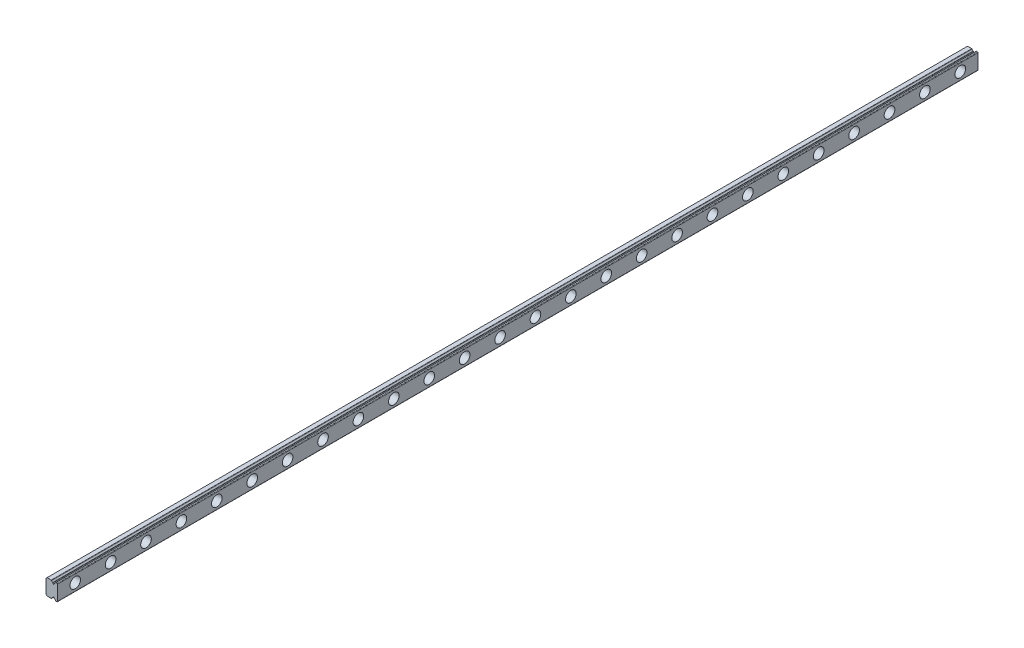
SolidWorks part; units mm, degrees
material "AISI 304"
ref_plane "前视基准面" through (0, 0, 0) normal (0, 0, 1) x (1, 0, 0)
ref_plane "上视基准面" through (0, 0, 0) normal (0, 1, 0) x (1, 0, 0)
ref_plane "右视基准面" through (0, 0, 0) normal (1, 0, 0) x (0, 0, -1)
sketch "草图1" plane through (0, 0, 0) normal (0, 0, 1) x (1, 0, 0)
  line L0 (0, 8.4) -> (0.6, 9)
  line L1 (0.6, 0) -> (2.9423, 0)
  line L2 (0, 0.6) -> (0, 8.4)
  line L3 (0.6, 9) -> (2.9423, 9)
  line L4 (6.5, 0.3) -> (6.5, 8.7)
  line L5 (0, 0.6) -> (0.6, 0)
  line L6 (4.25, 9) -> (4.25, 8) construction
  line L7 (4.25, 9) -> (4.25, 9.3) construction
  line L8 (3.85, 8) -> (3.85, 8.0351)
  line L9 (4.65, 8) -> (4.65, 8.0351)
  line L10 (5.5577, 9) -> (6.2, 9)
  line L11 (6.5, 4.5) -> (0, 4.5) construction
  line L12 (3.85, 8) -> (3.85, 8.0351)
  line L13 (4.65, 8) -> (4.65, 8.0351)
  line L14 (4.25, 0) -> (4.25, -0.3) construction
  line L15 (4.25, 0) -> (4.25, 1) construction
  line L16 (4.65, 1) -> (4.65, 0.9649)
  line L17 (3.85, 1) -> (3.85, 0.9649)
  line L18 (4.65, 1) -> (4.65, 0.9649)
  line L19 (3.85, 1) -> (3.85, 0.9649)
  line L20 (5.5577, 0) -> (6.2, 0)
  arc A0 (3.85, 8) -> (4.65, 8) centre (4.25, 8) ccw
  arc A1 (3.1291, 8.8714) -> (3.7357, 8.2158) centre (4.25, 9.3) ccw
  arc A2 (4.7643, 8.2158) -> (5.3709, 8.8714) centre (4.25, 9.3) ccw
  arc A3 (5.3709, 8.8714) -> (5.5577, 9) centre (5.5577, 8.8) cw
  arc A4 (4.65, 8.0351) -> (4.7643, 8.2158) centre (4.85, 8.0351) cw
  arc A5 (3.85, 8.0351) -> (3.7357, 8.2158) centre (3.65, 8.0351) ccw
  arc A6 (3.1291, 8.8714) -> (2.9423, 9) centre (2.9423, 8.8) ccw
  arc A7 (3.1291, 8.8714) -> (2.9423, 9) centre (2.9423, 8.8) ccw
  arc A8 (5.3709, 8.8714) -> (5.5577, 9) centre (5.5577, 8.8) cw
  arc A9 (4.65, 8.0351) -> (4.7643, 8.2158) centre (4.85, 8.0351) cw
  arc A10 (3.85, 8.0351) -> (3.7357, 8.2158) centre (3.65, 8.0351) ccw
  arc A11 (3.7357, 8.2158) -> (3.1291, 8.8714) centre (4.25, 9.3) cw
  arc A12 (5.3709, 8.8714) -> (4.7643, 8.2158) centre (4.25, 9.3) cw
  arc A13 (5.3709, 0.1286) -> (5.5577, 0) centre (5.5577, 0.2) ccw
  arc A14 (3.1291, 0.1286) -> (2.9423, 0) centre (2.9423, 0.2) cw
  arc A15 (5.3709, 0.1286) -> (4.7643, 0.7842) centre (4.25, -0.3) ccw
  arc A16 (3.7357, 0.7842) -> (3.1291, 0.1286) centre (4.25, -0.3) ccw
  arc A17 (3.85, 0.9649) -> (3.7357, 0.7842) centre (3.65, 0.9649) cw
  arc A18 (4.65, 0.9649) -> (4.7643, 0.7842) centre (4.85, 0.9649) ccw
  arc A19 (3.85, 0.9649) -> (3.7357, 0.7842) centre (3.65, 0.9649) cw
  arc A20 (4.65, 0.9649) -> (4.7643, 0.7842) centre (4.85, 0.9649) ccw
  arc A21 (4.7643, 0.7842) -> (5.3709, 0.1286) centre (4.25, -0.3) cw
  arc A22 (3.1291, 0.1286) -> (3.7357, 0.7842) centre (4.25, -0.3) cw
  arc A23 (3.85, 1) -> (4.65, 1) centre (4.25, 1) cw
  arc A24 (6.2, 0) -> (6.5, 0.3) centre (6.2, 0.3) ccw
  arc A25 (6.2, 9) -> (6.5, 8.7) centre (6.2, 8.7) cw
  point P0 (0, 0)
  point P2 (0, 9)
  point P24 (5.4119, 9)
  point P27 (4.65, 8.1686)
  point P49 (4.65, 0.8314)
  point P50 (5.4119, 0)
  point P53 (6.5, 0)
  dimension "D3" = 1
  dimension "D7" = 0.8
  dimension "D9" = 2.4
  dimension "D10" = 0.2
  dimension "D11" = 0.3
  dimension "D1" = 6.5
  dimension "D2" = 9
  dimension "D4" = 2.25
  dimension "D8" = 0.3
extrude "凸台-拉伸1" add sketch "草图1" along normal blind 400 contours A25 L10 A3 A2 A4 L9 A0 L8 A5 A1 A6 L3 L0 L2 L5 L1 A14 A16 A17 L17 A23 L16 A18 A15 A13 L20 A24 L4 region at (3.1975, 4.5, 0)
sketch "草图2" plane through (6.5, 0, 0) normal (1, 0, 0) x (0, 0, -1)
  line L0 (-400, 4.5) -> (-390, 4.5) construction
  line L1 (-400, 0.3) -> (-400, 8.7) construction
  line L2 (-390, 4.5) -> (-10, 4.5) construction
  line L3 (-10, 4.5) -> (0, 4.5) construction
  line L4 (0, 0.3) -> (0, 8.7) construction
  line L5 (-10, 4.5) -> (-30, 4.5) construction
  circle A0 centre (-10, 4.5) radius 3
  circle A1 centre (-30, 4.5) radius 3
  circle A2 centre (-50, 4.5) radius 3
  circle A3 centre (-70, 4.5) radius 3
  circle A4 centre (-90, 4.5) radius 3
  circle A5 centre (-110, 4.5) radius 3
  circle A6 centre (-130, 4.5) radius 3
  circle A7 centre (-150, 4.5) radius 3
  circle A8 centre (-170, 4.5) radius 3
  circle A9 centre (-190, 4.5) radius 3
  circle A10 centre (-210, 4.5) radius 3
  circle A11 centre (-230, 4.5) radius 3
  circle A12 centre (-250, 4.5) radius 3
  circle A13 centre (-270, 4.5) radius 3
  circle A14 centre (-290, 4.5) radius 3
  circle A15 centre (-310, 4.5) radius 3
  circle A16 centre (-330, 4.5) radius 3
  circle A17 centre (-350, 4.5) radius 3
  circle A18 centre (-370, 4.5) radius 3
  circle A19 centre (-390, 4.5) radius 3
  circle A20 centre (-410, 4.5) radius 3
  circle A21 centre (-430, 4.5) radius 3
  circle A22 centre (-450, 4.5) radius 3
  circle A23 centre (-470, 4.5) radius 3
  circle A24 centre (-490, 4.5) radius 3
  circle A25 centre (-510, 4.5) radius 3
  circle A26 centre (-530, 4.5) radius 3
  circle A27 centre (-550, 4.5) radius 3
  circle A28 centre (-570, 4.5) radius 3
  circle A29 centre (-590, 4.5) radius 3
  circle A30 centre (-610, 4.5) radius 3
  circle A31 centre (-630, 4.5) radius 3
  circle A32 centre (-650, 4.5) radius 3
  circle A33 centre (-670, 4.5) radius 3
  circle A34 centre (-690, 4.5) radius 3
  circle A35 centre (-710, 4.5) radius 3
  circle A36 centre (-730, 4.5) radius 3
  circle A37 centre (-750, 4.5) radius 3
  circle A38 centre (-770, 4.5) radius 3
  circle A39 centre (-790, 4.5) radius 3
  circle A40 centre (-810, 4.5) radius 3
  circle A41 centre (-830, 4.5) radius 3
  circle A42 centre (-850, 4.5) radius 3
  circle A43 centre (-870, 4.5) radius 3
  circle A44 centre (-890, 4.5) radius 3
  circle A45 centre (-910, 4.5) radius 3
  circle A46 centre (-930, 4.5) radius 3
  circle A47 centre (-950, 4.5) radius 3
  circle A48 centre (-970, 4.5) radius 3
  circle A49 centre (-990, 4.5) radius 3
  circle A50 centre (-1010, 4.5) radius 3
  circle A51 centre (-1030, 4.5) radius 3
  circle A52 centre (-1050, 4.5) radius 3
  circle A53 centre (-1070, 4.5) radius 3
  circle A54 centre (-1090, 4.5) radius 3
  circle A55 centre (-1110, 4.5) radius 3
  circle A56 centre (-1130, 4.5) radius 3
  circle A57 centre (-1150, 4.5) radius 3
  circle A58 centre (-1170, 4.5) radius 3
  circle A59 centre (-1190, 4.5) radius 3
  circle A60 centre (-1210, 4.5) radius 3
  circle A61 centre (-1230, 4.5) radius 3
  circle A62 centre (-1250, 4.5) radius 3
  circle A63 centre (-1270, 4.5) radius 3
  circle A64 centre (-1290, 4.5) radius 3
  circle A65 centre (-1310, 4.5) radius 3
  circle A66 centre (-1330, 4.5) radius 3
  circle A67 centre (-1350, 4.5) radius 3
  circle A68 centre (-1370, 4.5) radius 3
  circle A69 centre (-1390, 4.5) radius 3
  circle A70 centre (-1410, 4.5) radius 3
  circle A71 centre (-1430, 4.5) radius 3
  circle A72 centre (-1450, 4.5) radius 3
  circle A73 centre (-1470, 4.5) radius 3
  circle A74 centre (-1490, 4.5) radius 3
  circle A75 centre (-1510, 4.5) radius 3
  circle A76 centre (-1530, 4.5) radius 3
  circle A77 centre (-1550, 4.5) radius 3
  circle A78 centre (-1570, 4.5) radius 3
  circle A79 centre (-1590, 4.5) radius 3
  circle A80 centre (-1610, 4.5) radius 3
  circle A81 centre (-1630, 4.5) radius 3
  circle A82 centre (-1650, 4.5) radius 3
  circle A83 centre (-1670, 4.5) radius 3
  circle A84 centre (-1690, 4.5) radius 3
  circle A85 centre (-1710, 4.5) radius 3
  circle A86 centre (-1730, 4.5) radius 3
  circle A87 centre (-1750, 4.5) radius 3
  circle A88 centre (-1770, 4.5) radius 3
  circle A89 centre (-1790, 4.5) radius 3
  circle A90 centre (-1810, 4.5) radius 3
  circle A91 centre (-1830, 4.5) radius 3
  circle A92 centre (-1850, 4.5) radius 3
  circle A93 centre (-1870, 4.5) radius 3
  circle A94 centre (-1890, 4.5) radius 3
  circle A95 centre (-1910, 4.5) radius 3
  circle A96 centre (-1930, 4.5) radius 3
  circle A97 centre (-1950, 4.5) radius 3
  circle A98 centre (-1970, 4.5) radius 3
  circle A99 centre (-1990, 4.5) radius 3
  circle A100 centre (-2010, 4.5) radius 3
  circle A101 centre (-2030, 4.5) radius 3
  circle A102 centre (-2050, 4.5) radius 3
  circle A103 centre (-2070, 4.5) radius 3
  circle A104 centre (-2090, 4.5) radius 3
  circle A105 centre (-2110, 4.5) radius 3
  circle A106 centre (-2130, 4.5) radius 3
  circle A107 centre (-2150, 4.5) radius 3
  circle A108 centre (-2170, 4.5) radius 3
  circle A109 centre (-2190, 4.5) radius 3
  circle A110 centre (-2210, 4.5) radius 3
  circle A111 centre (-2230, 4.5) radius 3
  circle A112 centre (-2250, 4.5) radius 3
  circle A113 centre (-2270, 4.5) radius 3
  circle A114 centre (-2290, 4.5) radius 3
  circle A115 centre (-2310, 4.5) radius 3
  circle A116 centre (-2330, 4.5) radius 3
  circle A117 centre (-2350, 4.5) radius 3
  circle A118 centre (-2370, 4.5) radius 3
  circle A119 centre (-2390, 4.5) radius 3
  circle A120 centre (-2410, 4.5) radius 3
  circle A121 centre (-2430, 4.5) radius 3
  circle A122 centre (-2450, 4.5) radius 3
  circle A123 centre (-2470, 4.5) radius 3
  dimension "D2" = 6
  dimension "D1" = 10
  dimension "D4" = 20
  dimension "D3" = 25
  dimension "D5" = 100
extrude "切除-拉伸1" cut sketch "草图2" against normal blind 4.5
sketch "草图3" plane through (2, 0, 0) normal (1, 0, 0) x (0, 0, -1)
  line L0 (-10, 4.5) -> (-30, 4.5) construction
  circle A0 centre (-10, 4.5) radius 1.75
  circle A1 centre (-30, 4.5) radius 1.75
  circle A2 centre (-50, 4.5) radius 1.75
  circle A3 centre (-70, 4.5) radius 1.75
  circle A4 centre (-90, 4.5) radius 1.75
  circle A5 centre (-110, 4.5) radius 1.75
  circle A6 centre (-130, 4.5) radius 1.75
  circle A7 centre (-150, 4.5) radius 1.75
  circle A8 centre (-170, 4.5) radius 1.75
  circle A9 centre (-190, 4.5) radius 1.75
  circle A10 centre (-210, 4.5) radius 1.75
  circle A11 centre (-230, 4.5) radius 1.75
  circle A12 centre (-250, 4.5) radius 1.75
  circle A13 centre (-270, 4.5) radius 1.75
  circle A14 centre (-290, 4.5) radius 1.75
  circle A15 centre (-310, 4.5) radius 1.75
  circle A16 centre (-330, 4.5) radius 1.75
  circle A17 centre (-350, 4.5) radius 1.75
  circle A18 centre (-370, 4.5) radius 1.75
  circle A19 centre (-390, 4.5) radius 1.75
  circle A20 centre (-410, 4.5) radius 1.75
  circle A21 centre (-430, 4.5) radius 1.75
  circle A22 centre (-450, 4.5) radius 1.75
  circle A23 centre (-470, 4.5) radius 1.75
  circle A24 centre (-490, 4.5) radius 1.75
  circle A25 centre (-510, 4.5) radius 1.75
  circle A26 centre (-530, 4.5) radius 1.75
  circle A27 centre (-550, 4.5) radius 1.75
  circle A28 centre (-570, 4.5) radius 1.75
  circle A29 centre (-590, 4.5) radius 1.75
  circle A30 centre (-610, 4.5) radius 1.75
  circle A31 centre (-630, 4.5) radius 1.75
  circle A32 centre (-650, 4.5) radius 1.75
  circle A33 centre (-670, 4.5) radius 1.75
  circle A34 centre (-690, 4.5) radius 1.75
  circle A35 centre (-710, 4.5) radius 1.75
  circle A36 centre (-730, 4.5) radius 1.75
  circle A37 centre (-750, 4.5) radius 1.75
  circle A38 centre (-770, 4.5) radius 1.75
  circle A39 centre (-790, 4.5) radius 1.75
  circle A40 centre (-810, 4.5) radius 1.75
  circle A41 centre (-830, 4.5) radius 1.75
  circle A42 centre (-850, 4.5) radius 1.75
  circle A43 centre (-870, 4.5) radius 1.75
  circle A44 centre (-890, 4.5) radius 1.75
  circle A45 centre (-910, 4.5) radius 1.75
  circle A46 centre (-930, 4.5) radius 1.75
  circle A47 centre (-950, 4.5) radius 1.75
  circle A48 centre (-970, 4.5) radius 1.75
  circle A49 centre (-990, 4.5) radius 1.75
  circle A50 centre (-1010, 4.5) radius 1.75
  circle A51 centre (-1030, 4.5) radius 1.75
  circle A52 centre (-1050, 4.5) radius 1.75
  circle A53 centre (-1070, 4.5) radius 1.75
  dimension "D1" = 3.5
  dimension "D3" = 20
  dimension "D2" = 25
  dimension "D4" = 30
extrude "切除-拉伸2" cut sketch "草图3" against normal through all
sketch "草图4" plane through (0, 0, 400) normal (0, 0, 1) x (1, 0, 0)
  line L12 (6.2, 9) -> (5.5577, 9)
  line L13 (4.65, 8.0351) -> (4.65, 8)
  line L14 (3.85, 8) -> (3.85, 8.0351)
  line L15 (2.9423, 9) -> (0.6, 9)
  line L16 (0.6, 9) -> (0, 8.4)
  line L17 (0, 8.4) -> (0, 0.6)
  line L18 (0, 0.6) -> (0.6, 0)
  line L19 (0.6, 0) -> (2.9423, 0)
  line L20 (3.85, 0.9649) -> (3.85, 1)
  line L21 (4.65, 1) -> (4.65, 0.9649)
  line L22 (5.5577, 0) -> (6.2, 0)
  line L23 (6.5, 0.3) -> (6.5, 8.7)
  line L24 (6.2, 9) -> (5.5577, 9)
  line L25 (4.65, 8.0351) -> (4.65, 8)
  line L26 (3.85, 8) -> (3.85, 8.0351)
  line L27 (2.9423, 9) -> (0.6, 9)
  line L28 (0.6, 9) -> (0, 8.4)
  line L29 (0, 8.4) -> (0, 0.6)
  line L30 (0, 0.6) -> (0.6, 0)
  line L31 (0.6, 0) -> (2.9423, 0)
  line L32 (3.85, 0.9649) -> (3.85, 1)
  line L33 (4.65, 1) -> (4.65, 0.9649)
  line L34 (5.5577, 0) -> (6.2, 0)
  line L35 (6.5, 0.3) -> (6.5, 8.7)
  arc A16 (6.5, 8.7) -> (6.2, 9) centre (6.2, 8.7) ccw
  arc A17 (5.5577, 9) -> (5.3709, 8.8714) centre (5.5577, 8.8) ccw
  arc A18 (4.7643, 8.2158) -> (5.3709, 8.8714) centre (4.25, 9.3) ccw
  arc A19 (4.7643, 8.2158) -> (4.65, 8.0351) centre (4.85, 8.0351) ccw
  arc A20 (3.85, 8) -> (4.65, 8) centre (4.25, 8) ccw
  arc A21 (3.85, 8.0351) -> (3.7357, 8.2158) centre (3.65, 8.0351) ccw
  arc A22 (3.1291, 8.8714) -> (3.7357, 8.2158) centre (4.25, 9.3) ccw
  arc A23 (3.1291, 8.8714) -> (2.9423, 9) centre (2.9423, 8.8) ccw
  arc A24 (2.9423, 0) -> (3.1291, 0.1286) centre (2.9423, 0.2) ccw
  arc A25 (3.7357, 0.7842) -> (3.1291, 0.1286) centre (4.25, -0.3) ccw
  arc A26 (3.7357, 0.7842) -> (3.85, 0.9649) centre (3.65, 0.9649) ccw
  arc A27 (4.65, 1) -> (3.85, 1) centre (4.25, 1) ccw
  arc A28 (4.65, 0.9649) -> (4.7643, 0.7842) centre (4.85, 0.9649) ccw
  arc A29 (5.3709, 0.1286) -> (4.7643, 0.7842) centre (4.25, -0.3) ccw
  arc A30 (5.3709, 0.1286) -> (5.5577, 0) centre (5.5577, 0.2) ccw
  arc A31 (6.2, 0) -> (6.5, 0.3) centre (6.2, 0.3) ccw
  arc A32 (6.5, 8.7) -> (6.2, 9) centre (6.2, 8.7) ccw
  arc A33 (5.5577, 9) -> (5.3709, 8.8714) centre (5.5577, 8.8) ccw
  arc A34 (4.7643, 8.2158) -> (5.3709, 8.8714) centre (4.25, 9.3) ccw
  arc A35 (4.7643, 8.2158) -> (4.65, 8.0351) centre (4.85, 8.0351) ccw
  arc A36 (3.85, 8) -> (4.65, 8) centre (4.25, 8) ccw
  arc A37 (3.85, 8.0351) -> (3.7357, 8.2158) centre (3.65, 8.0351) ccw
  arc A38 (3.1291, 8.8714) -> (3.7357, 8.2158) centre (4.25, 9.3) ccw
  arc A39 (3.1291, 8.8714) -> (2.9423, 9) centre (2.9423, 8.8) ccw
  arc A40 (2.9423, 0) -> (3.1291, 0.1286) centre (2.9423, 0.2) ccw
  arc A41 (3.7357, 0.7842) -> (3.1291, 0.1286) centre (4.25, -0.3) ccw
  arc A42 (3.7357, 0.7842) -> (3.85, 0.9649) centre (3.65, 0.9649) ccw
  arc A43 (4.65, 1) -> (3.85, 1) centre (4.25, 1) ccw
  arc A44 (4.65, 0.9649) -> (4.7643, 0.7842) centre (4.85, 0.9649) ccw
  arc A45 (5.3709, 0.1286) -> (4.7643, 0.7842) centre (4.25, -0.3) ccw
  arc A46 (5.3709, 0.1286) -> (5.5577, 0) centre (5.5577, 0.2) ccw
  arc A47 (6.2, 0) -> (6.5, 0.3) centre (6.2, 0.3) ccw
  dimension "D1" = 0
sketch "草图5" plane through (0, 0, 0) normal (0, 0, -1) x (-1, 0, 0)
  line L12 (-6.5, 8.7) -> (-6.5, 0.3)
  line L13 (-6.2, 0) -> (-5.5577, 0)
  line L14 (-4.65, 0.9649) -> (-4.65, 1)
  line L15 (-3.85, 1) -> (-3.85, 0.9649)
  line L16 (-2.9423, 0) -> (-0.6, 0)
  line L17 (-0.6, 0) -> (0, 0.6)
  line L18 (0, 0.6) -> (0, 8.4)
  line L19 (0, 8.4) -> (-0.6, 9)
  line L20 (-0.6, 9) -> (-2.9423, 9)
  line L21 (-3.85, 8.0351) -> (-3.85, 8)
  line L22 (-4.65, 8) -> (-4.65, 8.0351)
  line L23 (-5.5577, 9) -> (-6.2, 9)
  line L24 (-6.5, 8.7) -> (-6.5, 0.3)
  line L25 (-6.2, 0) -> (-5.5577, 0)
  line L26 (-4.65, 0.9649) -> (-4.65, 1)
  line L27 (-3.85, 1) -> (-3.85, 0.9649)
  line L28 (-2.9423, 0) -> (-0.6, 0)
  line L29 (-0.6, 0) -> (0, 0.6)
  line L30 (0, 0.6) -> (0, 8.4)
  line L31 (0, 8.4) -> (-0.6, 9)
  line L32 (-0.6, 9) -> (-2.9423, 9)
  line L33 (-3.85, 8.0351) -> (-3.85, 8)
  line L34 (-4.65, 8) -> (-4.65, 8.0351)
  line L35 (-5.5577, 9) -> (-6.2, 9)
  arc A16 (-6.2, 9) -> (-6.5, 8.7) centre (-6.2, 8.7) ccw
  arc A17 (-6.5, 0.3) -> (-6.2, 0) centre (-6.2, 0.3) ccw
  arc A18 (-5.5577, 0) -> (-5.3709, 0.1286) centre (-5.5577, 0.2) ccw
  arc A19 (-4.7643, 0.7842) -> (-5.3709, 0.1286) centre (-4.25, -0.3) ccw
  arc A20 (-4.7643, 0.7842) -> (-4.65, 0.9649) centre (-4.85, 0.9649) ccw
  arc A21 (-3.85, 1) -> (-4.65, 1) centre (-4.25, 1) ccw
  arc A22 (-3.85, 0.9649) -> (-3.7357, 0.7842) centre (-3.65, 0.9649) ccw
  arc A23 (-3.1291, 0.1286) -> (-3.7357, 0.7842) centre (-4.25, -0.3) ccw
  arc A24 (-3.1291, 0.1286) -> (-2.9423, 0) centre (-2.9423, 0.2) ccw
  arc A25 (-2.9423, 9) -> (-3.1291, 8.8714) centre (-2.9423, 8.8) ccw
  arc A26 (-3.7357, 8.2158) -> (-3.1291, 8.8714) centre (-4.25, 9.3) ccw
  arc A27 (-3.7357, 8.2158) -> (-3.85, 8.0351) centre (-3.65, 8.0351) ccw
  arc A28 (-4.65, 8) -> (-3.85, 8) centre (-4.25, 8) ccw
  arc A29 (-4.65, 8.0351) -> (-4.7643, 8.2158) centre (-4.85, 8.0351) ccw
  arc A30 (-5.3709, 8.8714) -> (-4.7643, 8.2158) centre (-4.25, 9.3) ccw
  arc A31 (-5.3709, 8.8714) -> (-5.5577, 9) centre (-5.5577, 8.8) ccw
  arc A32 (-6.2, 9) -> (-6.5, 8.7) centre (-6.2, 8.7) ccw
  arc A33 (-6.5, 0.3) -> (-6.2, 0) centre (-6.2, 0.3) ccw
  arc A34 (-5.5577, 0) -> (-5.3709, 0.1286) centre (-5.5577, 0.2) ccw
  arc A35 (-4.7643, 0.7842) -> (-5.3709, 0.1286) centre (-4.25, -0.3) ccw
  arc A36 (-4.7643, 0.7842) -> (-4.65, 0.9649) centre (-4.85, 0.9649) ccw
  arc A37 (-3.85, 1) -> (-4.65, 1) centre (-4.25, 1) ccw
  arc A38 (-3.85, 0.9649) -> (-3.7357, 0.7842) centre (-3.65, 0.9649) ccw
  arc A39 (-3.1291, 0.1286) -> (-3.7357, 0.7842) centre (-4.25, -0.3) ccw
  arc A40 (-3.1291, 0.1286) -> (-2.9423, 0) centre (-2.9423, 0.2) ccw
  arc A41 (-2.9423, 9) -> (-3.1291, 8.8714) centre (-2.9423, 8.8) ccw
  arc A42 (-3.7357, 8.2158) -> (-3.1291, 8.8714) centre (-4.25, 9.3) ccw
  arc A43 (-3.7357, 8.2158) -> (-3.85, 8.0351) centre (-3.65, 8.0351) ccw
  arc A44 (-4.65, 8) -> (-3.85, 8) centre (-4.25, 8) ccw
  arc A45 (-4.65, 8.0351) -> (-4.7643, 8.2158) centre (-4.85, 8.0351) ccw
  arc A46 (-5.3709, 8.8714) -> (-4.7643, 8.2158) centre (-4.25, 9.3) ccw
  arc A47 (-5.3709, 8.8714) -> (-5.5577, 9) centre (-5.5577, 8.8) ccw
  dimension "D1" = 0
extrude "切除-拉伸4" cut sketch "草图5" against normal blind 80
sketch "草图6" plane through (0, 0, 400) normal (0, 0, 1) x (1, 0, 0)
  line L12 (6.2, 9) -> (5.5577, 9)
  line L13 (4.65, 8.0351) -> (4.65, 8)
  line L14 (3.85, 8) -> (3.85, 8.0351)
  line L15 (2.9423, 9) -> (0.6, 9)
  line L16 (0.6, 9) -> (0, 8.4)
  line L17 (0, 8.4) -> (0, 0.6)
  line L18 (0, 0.6) -> (0.6, 0)
  line L19 (0.6, 0) -> (2.9423, 0)
  line L20 (3.85, 0.9649) -> (3.85, 1)
  line L21 (4.65, 1) -> (4.65, 0.9649)
  line L22 (5.5577, 0) -> (6.2, 0)
  line L23 (6.5, 0.3) -> (6.5, 8.7)
  line L24 (6.2, 9) -> (5.5577, 9)
  line L25 (4.65, 8.0351) -> (4.65, 8)
  line L26 (3.85, 8) -> (3.85, 8.0351)
  line L27 (2.9423, 9) -> (0.6, 9)
  line L28 (0.6, 9) -> (0, 8.4)
  line L29 (0, 8.4) -> (0, 0.6)
  line L30 (0, 0.6) -> (0.6, 0)
  line L31 (0.6, 0) -> (2.9423, 0)
  line L32 (3.85, 0.9649) -> (3.85, 1)
  line L33 (4.65, 1) -> (4.65, 0.9649)
  line L34 (5.5577, 0) -> (6.2, 0)
  line L35 (6.5, 0.3) -> (6.5, 8.7)
  arc A16 (6.5, 8.7) -> (6.2, 9) centre (6.2, 8.7) ccw
  arc A17 (5.5577, 9) -> (5.3709, 8.8714) centre (5.5577, 8.8) ccw
  arc A18 (4.7643, 8.2158) -> (5.3709, 8.8714) centre (4.25, 9.3) ccw
  arc A19 (4.7643, 8.2158) -> (4.65, 8.0351) centre (4.85, 8.0351) ccw
  arc A20 (3.85, 8) -> (4.65, 8) centre (4.25, 8) ccw
  arc A21 (3.85, 8.0351) -> (3.7357, 8.2158) centre (3.65, 8.0351) ccw
  arc A22 (3.1291, 8.8714) -> (3.7357, 8.2158) centre (4.25, 9.3) ccw
  arc A23 (3.1291, 8.8714) -> (2.9423, 9) centre (2.9423, 8.8) ccw
  arc A24 (2.9423, 0) -> (3.1291, 0.1286) centre (2.9423, 0.2) ccw
  arc A25 (3.7357, 0.7842) -> (3.1291, 0.1286) centre (4.25, -0.3) ccw
  arc A26 (3.7357, 0.7842) -> (3.85, 0.9649) centre (3.65, 0.9649) ccw
  arc A27 (4.65, 1) -> (3.85, 1) centre (4.25, 1) ccw
  arc A28 (4.65, 0.9649) -> (4.7643, 0.7842) centre (4.85, 0.9649) ccw
  arc A29 (5.3709, 0.1286) -> (4.7643, 0.7842) centre (4.25, -0.3) ccw
  arc A30 (5.3709, 0.1286) -> (5.5577, 0) centre (5.5577, 0.2) ccw
  arc A31 (6.2, 0) -> (6.5, 0.3) centre (6.2, 0.3) ccw
  arc A32 (6.5, 8.7) -> (6.2, 9) centre (6.2, 8.7) ccw
  arc A33 (5.5577, 9) -> (5.3709, 8.8714) centre (5.5577, 8.8) ccw
  arc A34 (4.7643, 8.2158) -> (5.3709, 8.8714) centre (4.25, 9.3) ccw
  arc A35 (4.7643, 8.2158) -> (4.65, 8.0351) centre (4.85, 8.0351) ccw
  arc A36 (3.85, 8) -> (4.65, 8) centre (4.25, 8) ccw
  arc A37 (3.85, 8.0351) -> (3.7357, 8.2158) centre (3.65, 8.0351) ccw
  arc A38 (3.1291, 8.8714) -> (3.7357, 8.2158) centre (4.25, 9.3) ccw
  arc A39 (3.1291, 8.8714) -> (2.9423, 9) centre (2.9423, 8.8) ccw
  arc A40 (2.9423, 0) -> (3.1291, 0.1286) centre (2.9423, 0.2) ccw
  arc A41 (3.7357, 0.7842) -> (3.1291, 0.1286) centre (4.25, -0.3) ccw
  arc A42 (3.7357, 0.7842) -> (3.85, 0.9649) centre (3.65, 0.9649) ccw
  arc A43 (4.65, 1) -> (3.85, 1) centre (4.25, 1) ccw
  arc A44 (4.65, 0.9649) -> (4.7643, 0.7842) centre (4.85, 0.9649) ccw
  arc A45 (5.3709, 0.1286) -> (4.7643, 0.7842) centre (4.25, -0.3) ccw
  arc A46 (5.3709, 0.1286) -> (5.5577, 0) centre (5.5577, 0.2) ccw
  arc A47 (6.2, 0) -> (6.5, 0.3) centre (6.2, 0.3) ccw
  dimension "D1" = 0
extrude "凸台-拉伸2" add sketch "草图6" along normal blind 200
sketch "草图7" plane through (0, 0, 0) normal (-1, 0, 0) x (0, 0, 1)
  circle A0 centre (390, 4.5) radius 1.75 construction
  circle A1 centre (390, 4.5) radius 1.75
  circle A2 centre (410, 4.5) radius 1.75
  circle A3 centre (430, 4.5) radius 1.75
  circle A4 centre (450, 4.5) radius 1.75
  circle A5 centre (470, 4.5) radius 1.75
  circle A6 centre (490, 4.5) radius 1.75
  circle A7 centre (510, 4.5) radius 1.75
  circle A8 centre (530, 4.5) radius 1.75
  circle A9 centre (550, 4.5) radius 1.75
  circle A10 centre (570, 4.5) radius 1.75
  circle A11 centre (590, 4.5) radius 1.75
  dimension "D1" = 11
extrude "切除-拉伸5" cut sketch "草图7" against normal blind 100
sketch "草图8" plane through (6.5, 0, 0) normal (1, 0, 0) x (0, 0, -1)
  circle A0 centre (-390, 4.5) radius 3 construction
  circle A1 centre (-390, 4.5) radius 3
  circle A2 centre (-410, 4.5) radius 3
  circle A3 centre (-430, 4.5) radius 3
  circle A4 centre (-450, 4.5) radius 3
  circle A5 centre (-470, 4.5) radius 3
  circle A6 centre (-490, 4.5) radius 3
  circle A7 centre (-510, 4.5) radius 3
  circle A8 centre (-530, 4.5) radius 3
  circle A9 centre (-550, 4.5) radius 3
  circle A10 centre (-570, 4.5) radius 3
  circle A11 centre (-590, 4.5) radius 3
  dimension "D1" = 11
extrude "切除-拉伸6" cut sketch "草图8" against normal blind 4.5
